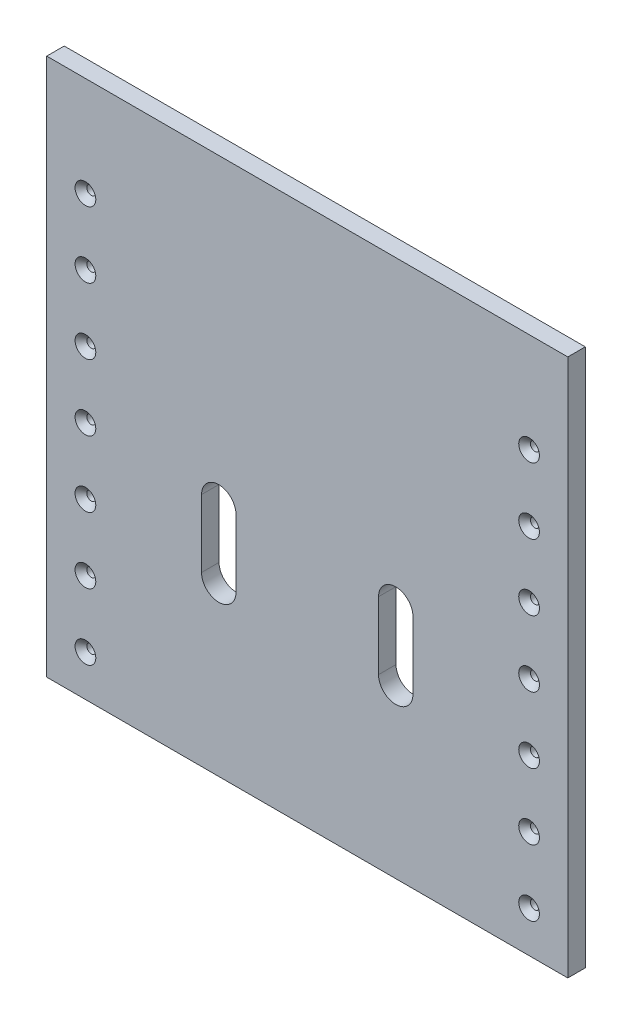
SolidWorks part; units mm, degrees
ref_plane "Front Plane" through (0, 0, 0) normal (0, 0, 1) x (1, 0, 0)
ref_plane "Top Plane" through (0, 0, 0) normal (0, 1, 0) x (1, 0, 0)
ref_plane "Right Plane" through (0, 0, 0) normal (1, 0, 0) x (0, 0, -1)
sketch "Sketch1" plane through (0, 0, 0) normal (0, 0, -1) x (1, 0, 0)
  line L1 (-203.2, 237) -> (-6.35, 237)
  line L2 (-203.2, 237) -> (-203.2, 33.8)
  line L3 (-203.2, 33.8) -> (-6.35, 33.8)
  line L4 (-6.35, 237) -> (-6.35, 33.8)
  dimension "D2" = 196.85
  dimension "D3" = 203.2
extrude "Boss-Extrude1" add sketch "Sketch1" along normal blind 6.604
sketch "Sketch2" plane through (0, 0, -6.604) normal (0, 0, -1) x (1, 0, 0)
  line L0 (-138.2, 180) -> (-138.2, 141.5) construction
  line L1 (-6.35, 237) -> (-203.2, 237) construction
  line L2 (-138.2, 180) -> (-138.2, 237) construction
  line L3 (-138.2, 173.5) -> (-138.2, 148) construction
  line L6 (-131.7, 173.5) -> (-131.7, 148)
  line L7 (-144.7, 173.5) -> (-144.7, 148)
  line L8 (-138.2, 160.75) -> (-203.2, 160.75) construction
  line L9 (-203.2, 237) -> (-203.2, 33.8) construction
  line L10 (-71.35, 180) -> (-71.35, 141.5) construction
  line L11 (-71.35, 180) -> (-71.35, 237) construction
  line L12 (-71.35, 173.5) -> (-71.35, 148) construction
  line L16 (-64.85, 173.5) -> (-64.85, 148)
  line L17 (-77.85, 173.5) -> (-77.85, 148)
  line L18 (-71.35, 160.75) -> (-6.35, 160.75) construction
  line L19 (-6.35, 33.8) -> (-6.35, 237) construction
  arc A2 (-131.7, 173.5) -> (-144.7, 173.5) centre (-138.2, 173.5) ccw
  arc A3 (-144.7, 148) -> (-131.7, 148) centre (-138.2, 148) ccw
  arc A6 (-64.85, 173.5) -> (-77.85, 173.5) centre (-71.35, 173.5) ccw
  arc A7 (-77.85, 148) -> (-64.85, 148) centre (-71.35, 148) ccw
  point P5 (-138.2, 160.75)
  point P18 (-71.35, 160.75)
  dimension "D4" = 6.5
  dimension "D6" = 57
  dimension "D5" = 6.5
  dimension "D1" = 65
  dimension "D2" = 57
  dimension "D3" = 38.5
  dimension "D7" = 65
  dimension "D8" = 38.5
extrude "Cut-Extrude7" cut sketch "Sketch2" against normal through all
ref_plane "Plane1" through (-104.775, 0, 0) normal (1, 0, 0) x (0, 0, -1)
sketch "Sketch4" plane through (0, 0, 0) normal (0, 0, 1) x (1, 0, 0)
  line L0 (-203.2, -33.8) -> (-6.35, -33.8) construction
  line L1 (-6.2816, -33.8) -> (-203.1316, -33.8)
  line L2 (-6.2816, -33.8) -> (-6.2816, -34.4096)
  line L3 (-6.2816, -34.4096) -> (-203.1316, -34.4096)
  line L4 (-203.1316, -33.8) -> (-203.1316, -34.4096)
  line L5 (-6.2816, -236.4678) -> (-6.2816, 2.5322) construction
  line L6 (-203.1316, 2.5322) -> (-203.1316, -236.4678) construction
  dimension "D1" = 0.6096
extrude "Boss-Extrude2" add sketch "Sketch4" along normal blind 12
sketch "Sketch8" plane through (0, 0, -6.604) normal (0, 0, -1) x (-1, 0, 0)
  circle A0 centre (185.47, -222) radius 3.75
  circle A1 centre (185.47, -197) radius 3.75
  circle A2 centre (185.47, -172) radius 3.75
  circle A3 centre (185.47, -147) radius 3.75
  circle A4 centre (185.47, -122) radius 3.75
  circle A5 centre (185.47, -97) radius 3.75
  dimension "D1" = 7.5
sketch "Sketch13" plane through (0, 0, 12) normal (0, 0, 1) x (1, 0, 0)
  line L1 (-6.2816, -34.4096) -> (-203.1316, -34.4096)
  line L2 (-6.2816, -34.4096) -> (-6.2816, -33.8)
  line L3 (-6.2816, -33.8) -> (-203.1316, -33.8)
  line L4 (-203.1316, -34.4096) -> (-203.1316, -33.8)
sketch "Sketch14" plane through (0, 0, 0) normal (0, 0, 1) x (1, 0, 0)
  line L0 (-6.35, -34.4096) -> (-6.35, -237) construction
  line L1 (-6.35, -59.904) -> (-203.2, -59.904)
  line L2 (-6.35, -59.904) -> (-6.35, -47.966)
  line L3 (-6.35, -47.966) -> (-203.2, -47.966)
  line L4 (-203.2, -59.904) -> (-203.2, -47.966)
  line L5 (-203.2, -237) -> (-203.2, -33.8) construction
  dimension "D1" = 11.938
extrude "Boss-Extrude3" add sketch "Sketch14" against normal up to surface (6.604 mm away) up to face at (-138.2, -160.75, -6.604)
extrude "Cut-Extrude9" cut sketch "Sketch13" against normal up to surface (12 mm away) up to face at (-71.35, -160.75, 0)
hole_wizard "CSK for M3 Flat Head Machine Screw3" positions "Sketch15" profile "Sketch16" countersink size "M3" standard "ANSI Metric" end condition through all
sketch "Sketch15" plane through (0, 0, 0) normal (0, 0, 1) x (1, 0, 0)
  point P18 (-188.5766, -71.4678)
  point P21 (-188.5766, -221.4678)
  point P24 (-188.5766, -196.4678)
  point P27 (-188.5766, -171.4678)
  point P30 (-188.5766, -146.4678)
  point P33 (-188.5766, -121.4678)
  point P36 (-188.5766, -96.4678)
  point P39 (-188.5766, -71.4678)
sketch "Sketch16" plane through (-188.5766, -71.4678, 0) normal (1, 0, 0) x (0, -1, 0)
  line L0 (0, 0) -> (0, 6.604)
  line L1 (0, 6.604) -> (1.7, 6.604)
  line L2 (1.7, 6.604) -> (1.7, 2.212)
  line L3 (1.7, 2.212) -> (3.912, 0)
  line L5 (3.912, 0) -> (0, 0)
  line L6 (-1.7, 2.212) -> (-3.912, 0) construction
  line L11 (0, -6.35) -> (0, 107.95) construction
  dimension "Thru Hole Dia." = 3.4
  dimension "Thru Hole Depth" = 6.604
  dimension "Near C'Sink Dia." = 7.824
  dimension "Near C'Sink Angle" = 90
ref_plane "Plane2" through (-104.775, 0, 0) normal (-1, 0, 0) x (0, 0, 1)
mirror "Mirror1" about plane through (-104.775, 0, 0) normal (-1, 0, 0) of "CSK for M3 Flat Head Machine Screw3"
